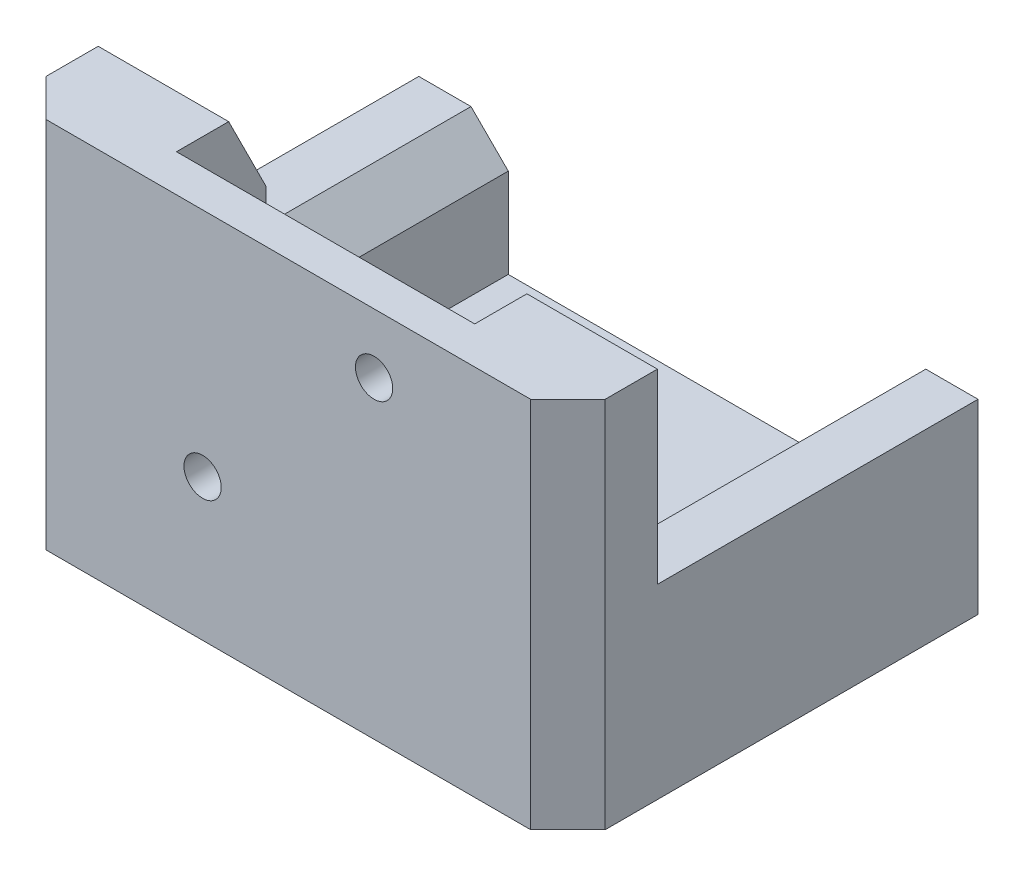
SolidWorks part; units mm, degrees
ref_plane "Front Plane" through (0, 0, 0) normal (0, 0, 1) x (1, 0, 0)
ref_plane "Top Plane" through (0, 0, 0) normal (0, 1, 0) x (1, 0, 0)
ref_plane "Right Plane" through (0, 0, 0) normal (1, 0, 0) x (0, 0, -1)
sketch "Sketch1" plane through (0, 0, 0) normal (0, 1, 0) x (1, 0, 0)
  line L1 (0, 0) -> (75, 0)
  line L2 (0, 0) -> (0, 17)
  line L3 (0, 17) -> (75, 17)
  line L4 (75, 0) -> (75, 17)
  dimension "D1" = 75
  dimension "D2" = 17
extrude "Boss-Extrude1" add sketch "Sketch1" along normal blind 50
sketch "Sketch2" plane through (0, 0, -17) normal (0, 0, -1) x (-1, 0, 0)
  line L1 (-75, 0) -> (-63, 0)
  line L2 (-75, 0) -> (-75, 25)
  line L3 (-75, 25) -> (-63, 25)
  line L4 (-63, 0) -> (-63, 25)
  line L5 (0, 0) -> (-12, 0)
  line L6 (0, 0) -> (0, 25)
  line L7 (0, 25) -> (-12, 25)
  line L8 (-12, 0) -> (-12, 25)
  dimension "D1" = 12
  dimension "D2" = 12
  dimension "D3" = 25
  dimension "D4" = 25
extrude "Boss-Extrude2" add sketch "Sketch2" along normal blind 38
sketch "Sketch3" plane through (0, 0, 0) normal (0, -1, 0) x (1, 0, 0)
  line L1 (0, 0) -> (75, 0)
  line L2 (0, 0) -> (0, -55)
  line L3 (0, -55) -> (75, -55)
  line L4 (75, 0) -> (75, -55)
extrude "Boss-Extrude3" add sketch "Sketch3" against normal blind 8
sketch "Sketch4" plane through (0, 0, 0) normal (0, -1, 0) x (-1, 0, 0)
  line L0 (0, 55) -> (0, 0) construction
  line L1 (0, 0) -> (-75, 0) construction
  line L2 (-75, 0) -> (-75, 55) construction
  circle A0 centre (-6.5, 8) radius 2.5
  circle A1 centre (-68.5, 8) radius 2.5
  circle A2 centre (-6.5, 42) radius 2.5
  circle A3 centre (-68.5, 42) radius 2.5
  point P12 (-6.5, 39.3024)
  point P15 (-68.5, 39.3024)
  dimension "D1" = 5
  dimension "D2" = 5
  dimension "D3" = 6.5
  dimension "D4" = 8
  dimension "D5" = 8
  dimension "D6" = 6.5
  dimension "D7" = 34
  dimension "D8" = 34
extrude "Cut-Extrude1" cut sketch "Sketch4" against normal blind 10
sketch "Sketch5" plane through (0, 0, -17) normal (0, 0, -1) x (-1, 0, 0)
  line L1 (-57.5, 50) -> (-17.5, 50)
  line L2 (-57.5, 50) -> (-57.5, 8)
  line L3 (-57.5, 8) -> (-17.5, 8)
  line L4 (-17.5, 50) -> (-17.5, 8)
  line L5 (-75, 50) -> (0, 50) construction
  line L6 (-12, 8) -> (-63, 8) construction
  point P6 (-37.5, 50)
  point P7 (-37.5, 50)
  dimension "D1" = 40
extrude "Cut-Extrude2" cut sketch "Sketch5" against normal blind 12
sketch "Sketch6" plane through (0, 0, -5) normal (0, 0, -1) x (-1, 0, 0)
  line L0 (-17.5, 50) -> (-57.5, 50) construction
  line L1 (-49, 42) -> (-26, 42)
  line L2 (-49, 42) -> (-49, 19)
  line L3 (-49, 19) -> (-26, 19)
  line L4 (-26, 42) -> (-26, 19)
  circle A0 centre (-49, 42) radius 2.5
  circle A1 centre (-26, 19) radius 2.5
  point P7 (-37.5, 50)
  point P8 (-37.5, 42)
  dimension "D4" = 5
  dimension "D5" = 5
  dimension "D1" = 23
  dimension "D2" = 23
  dimension "D3" = 8
extrude "Cut-Extrude3" cut sketch "Sketch6" against normal through all contours L1 A0 L2 | L2 A0 L1 | L3 A1 L4 | L4 A1 L3 region at (49.3537, 42.3537, -5) region at (47.939, 40.939, -5) region at (25.6463, 18.6463, -5) region at (27.061, 20.061, -5)
chamfer "Chamfer1" distance 5 angle 45 4 edges at (0, 25, 0) (75, 25, 0) (63, 25, -36) (12, 25, -36)
chamfer "Chamfer3" distance 10 distance2 5 2 edges at (0, 37.5, -17) (8.75, 50, -17) first distance on face at (9.4286, 26.5714, -17)
chamfer "Chamfer4" distance 5 distance2 10 2 edges at (66.25, 50, -17) (75, 37.5, -17) first distance on face at (37.5, 50, -7.8) first distance on face at (75, 25, -25.6667)
